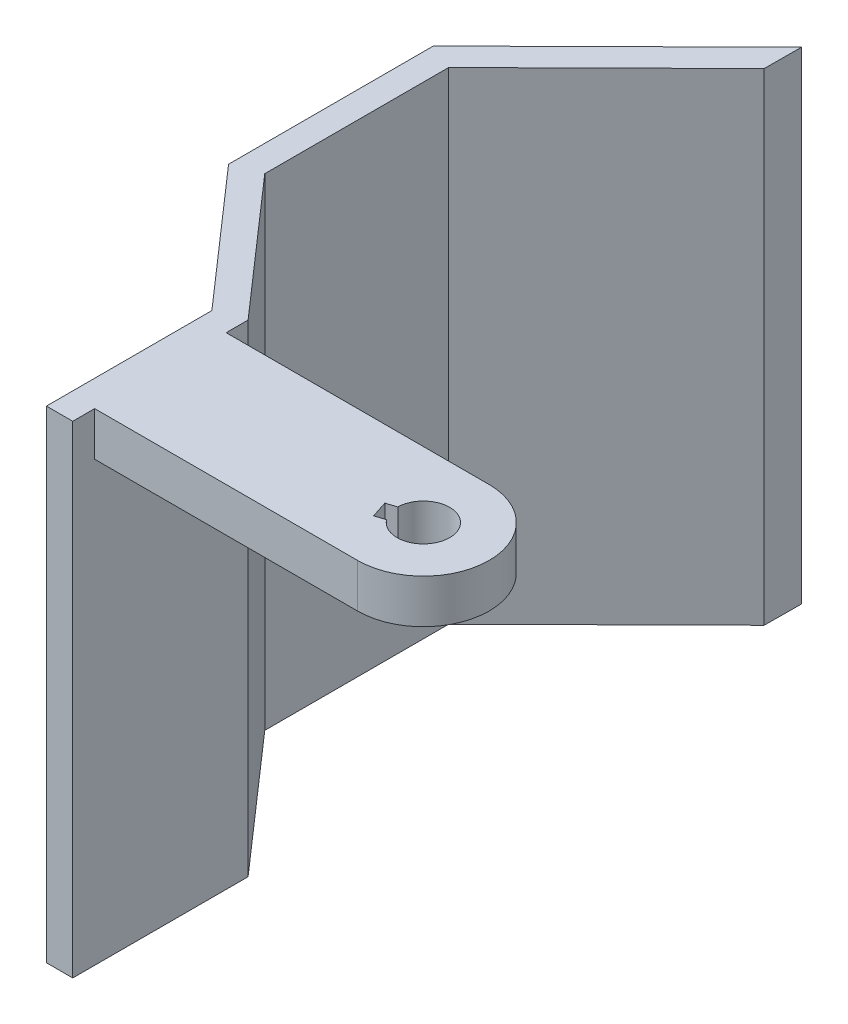
SolidWorks part; units mm, degrees
ref_plane "Front Plane" through (0, 0, 0) normal (0, 0, 1) x (1, 0, 0)
ref_plane "Top Plane" through (0, 0, 0) normal (0, 1, 0) x (1, 0, 0)
ref_plane "Right Plane" through (0, 0, 0) normal (1, 0, 0) x (0, 0, -1)
sketch "Sketch1" plane through (0, 0, 0) normal (0, 1, 0) x (1, 0, 0)
  line L0 (0, 0) -> (0, 18.8714)
  line L1 (0, 18.8714) -> (-13.5055, 34.2807)
  line L2 (-13.5055, 34.2807) -> (-13.5055, 57.6371)
  line L3 (-13.5055, 57.6371) -> (7.6165, 78.5217)
  line L9 (3, 0) -> (0, 0)
  line L10 (9.3102, 0) -> (0, 0) construction
  line L12 (3, 20) -> (-10.5055, 35.4093)
  line L13 (-10.5055, 35.4093) -> (-10.5055, 56.3845)
  line L14 (-10.5055, 56.3845) -> (7.5925, 74.2792)
  line L15 (7.5925, 74.2792) -> (7.6165, 78.5217)
  line L16 (9.3102, 3) -> (3, 3) construction
  line L18 (7.5925, 74.2792) -> (12.0785, 69.7422) construction
  line L19 (7.6165, 78.5217) -> (14.2117, 71.8516) construction
  line L20 (3, 0) -> (3, 20)
  line L21 (3, 3) -> (3, 20) construction
  line L22 (3, 2.5) -> (33, 2.5)
  line L23 (3, 17.5) -> (33, 17.5)
  arc A0 (33, 2.5) -> (33, 17.5) centre (33, 10) ccw
  point P22 (3, 10)
  dimension "D2" = 15
  dimension "D1" = 3
  dimension "D3" = 30
  dimension "D4" = 20
extrude "Boss-Extrude1" add sketch "Sketch1" along normal blind 55 contours L9 L20 L12 L13 L14 L15 L3 L2 L1 L0 region at (0.8131, 0, -9.4357)
extrude "Boss-Extrude2" add sketch "Sketch1<3>" against normal blind 5 from surface contours L22 A0 L23 L20 region at (20.9843, 0, -10) starting at face at (-2.6813, 55, -37.5384)
sketch "Sketch1<3>" plane through (0, 0, 0) normal (0, 1, 0) x (1, 0, 0) same geometry as "Sketch1"
ref_axis "GearAxis" through (33, 50, -10) along (0, 1, 0)
hole_wizard "M3 Clearance Hole1" positions "Sketch2" profile "Sketch3" hole size "M3" standard "ANSI Metric" end condition through all
sketch "Sketch2" plane through (0, 55, 0) normal (0, 1, 0) x (1, 0, 0)
  point P0 (33, 10)
sketch "Sketch3" plane through (33, 55, -10) normal (1, 0, 0) x (0, 0, 1)
  line L0 (0, 0) -> (0, 55)
  line L1 (0, 55) -> (1.7, 55)
  line L2 (1.7, 55) -> (1.7, 0.025)
  line L3 (1.7, 0.025) -> (1.725, 0)
  line L5 (1.725, 0) -> (0, 0)
  line L6 (-1.7, 0.025) -> (-1.725, 0) construction
  line L11 (0, -6.35) -> (0, 107.95) construction
  dimension "Thru Hole Dia." = 3.4
  dimension "Thru Hole Depth" = 55
  dimension "Near C'Sink Dia." = 3.45
  dimension "Near C'Sink Angle" = 90
sketch "Sketch4" plane through (0, 55, 0) normal (0, 1, 0) x (1, 0, 0)
  line L6 (30.001, 10.077) -> (28.8868, 9.715) construction
  line L7 (29.5048, 7.8129) -> (30.619, 8.1749) construction
  line L8 (28.8868, 9.715) -> (29.5048, 7.8129) construction
  line L9 (30.001, 10.077) -> (28.8868, 9.715)
  line L10 (29.5048, 7.8129) -> (30.619, 8.1749)
  line L11 (28.8868, 9.715) -> (29.5048, 7.8129)
  arc A2 (30.619, 8.1749) -> (30.001, 10.077) centre (33, 10) ccw construction
  arc A3 (30.619, 8.1749) -> (30.001, 10.077) centre (33, 10) ccw
extrude "Cut-Extrude1" cut sketch "Sketch4" against normal through all
